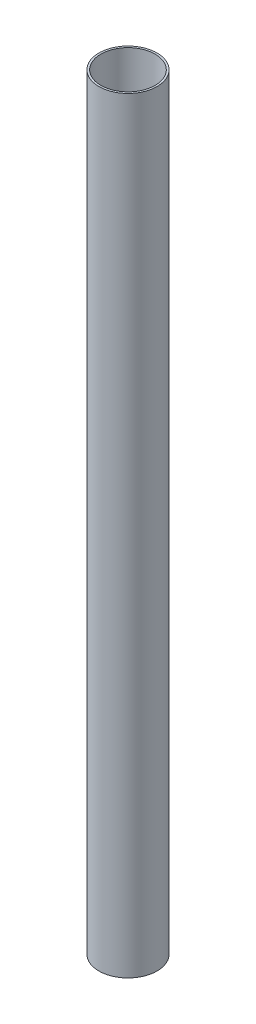
SolidWorks part; units mm, degrees
material "E-Glass Fiber"
ref_plane "Front Plane" through (0, 0, 0) normal (0, 0, 1) x (1, 0, 0)
ref_plane "Top Plane" through (0, 0, 0) normal (0, 1, 0) x (1, 0, 0)
ref_plane "Right Plane" through (0, 0, 0) normal (1, 0, 0) x (0, 0, -1)
sketch "Sketch1" plane through (0, 0, 0) normal (0, 0, 1) x (1, 0, 0)
  line L0 (0, 0) -> (0, -40.98) construction
  line L1 (28.9179, 37.2055) -> (28.9179, -724.7945) construction
  line L2 (26.9875, 37.2055) -> (28.9179, 37.2055)
  line L3 (26.9875, 37.2055) -> (26.9875, -724.7945)
  line L4 (26.9875, -724.7945) -> (28.9179, -724.7945)
  line L5 (28.9179, 37.2055) -> (28.9179, -724.7945)
  point P7 (26.1414, 37.1594)
  point P8 (0, 0)
  point P9 (26.9875, 37.2055)
  point P11 (28.9179, 37.2055)
  point P13 (28.9179, -48.4961)
  point P14 (28.9179, -464.933)
  point P15 (28.9179, -644.1547)
  point P18 (28.9179, -724.7945)
revolve "Revolve1" add sketch "Sketch1" angle 360 about L0
